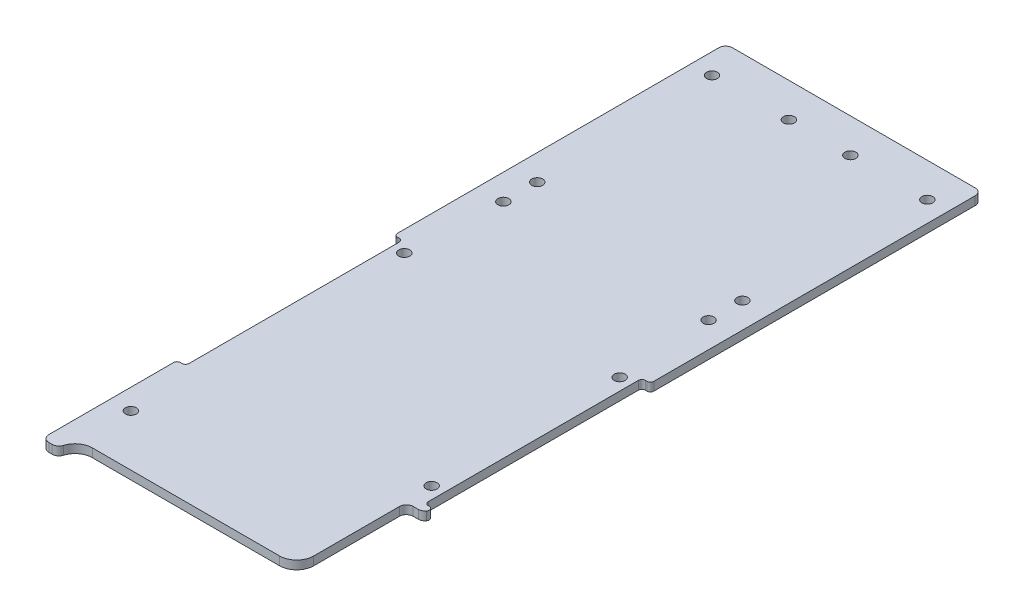
SolidWorks part; units mm, degrees
ref_plane "Front Plane" through (0, 0, 0) normal (0, 0, 1) x (1, 0, 0)
ref_plane "Top Plane" through (0, 0, 0) normal (0, 1, 0) x (1, 0, 0)
ref_plane "Right Plane" through (0, 0, 0) normal (1, 0, 0) x (0, 0, -1)
sketch "Sketch1" plane through (0, 0, 0) normal (0, 1, 0) x (1, 0, 0)
  line L0 (-39.9997, 0) -> (-39.9997, 114.3) construction
  line L1 (-47.625, 127) -> (47.625, 127)
  line L2 (-47.625, 127) -> (-47.625, -127)
  line L3 (-47.625, -127) -> (47.625, -127)
  line L4 (47.625, 127) -> (47.625, -127)
  line L5 (-47.625, 127) -> (47.625, -127) construction
  line L6 (-47.625, -127) -> (47.625, 127) construction
  line L7 (0, 0) -> (0, 127) construction
  line L8 (-39.9997, 0) -> (-39.9997, -101.6) construction
  line L9 (-39.9997, 0) -> (0, 0) construction
  line L10 (-41.275, -127) -> (-41.275, -120.65)
  line L11 (-41.275, -120.65) -> (41.275, -120.65)
  line L12 (41.275, -120.65) -> (41.275, -127)
  line L13 (-39.9997, 114.3) -> (-11.4247, 114.3) construction
  line L14 (39.9997, 114.3) -> (11.4247, 114.3) construction
  circle A0 centre (-39.9997, 114.3) radius 2.032
  circle A1 centre (-39.9997, 0) radius 2.032
  circle A2 centre (-39.9997, -101.6) radius 2.032
  circle A3 centre (39.9997, -101.6) radius 2.032
  circle A4 centre (39.9997, 0) radius 2.032
  circle A5 centre (39.9997, 114.3) radius 2.032
  circle A6 centre (-11.4247, 114.3) radius 2.032
  circle A7 centre (11.4247, 114.3) radius 2.032
  circle A8 centre (-39.9997, -69.85) radius 2.032
  circle A9 centre (39.9997, -69.85) radius 2.032
  point P0 (0, 0)
  dimension "D4" = 4.064
  dimension "D10" = 28.575
  dimension "D1" = 95.25
  dimension "D2" = 254
  dimension "D3" = 7.6253
  dimension "D5" = 12.7
  dimension "D6" = 25.4
  dimension "D7" = 6.35
  dimension "D8" = 6.35
  dimension "D9" = 6.35
  dimension "D11" = 69.85
extrude "Boss-Extrude1" add sketch "Sketch1" along normal blind 3.175 contours L4 L1 L2 L3 A4 A0 A1 A2 A3 A5 | A8 | A3 region at (0, 0, -2.6944) region at (39.9997, 0, 101.6) region at (-39.9997, 0, 69.85)
fillet "Fillet1" radius 2.54 4 edges at (-47.625, 1.5875, -127) (47.625, 1.5875, -127) (47.625, 1.5875, 127) (-47.625, 1.5875, 127)
fillet "Fillet2" radius 2.54 2 edges at (41.275, 1.5875, 127) (-41.275, 1.5875, 127)
fillet "Fillet3" radius 6.35 2 edges at (41.275, 1.5875, 120.65) (-41.275, 1.5875, 120.65)
sketch "Sketch2" plane through (0, 0, 0) normal (0, -1, 0) x (1, 0, 0)
  line L1 (43.815, 127) -> (45.085, 127) construction
  line L2 (40.6451, 123.5787) -> (40.6451, 79.8881)
  line L3 (40.6451, 79.8881) -> (47.625, 79.8881)
  line L11 (47.625, -124.46) -> (47.625, 124.46) construction
  line L12 (43.815, 127) -> (45.085, 127)
  line L13 (47.625, 79.8881) -> (47.625, 124.46)
  arc A0 (35.2956, 120.65) -> (41.3809, 125.1857) centre (35.2956, 127) ccw construction
  arc A1 (43.815, 127) -> (41.3809, 125.1857) centre (43.815, 124.46) ccw construction
  arc A2 (47.625, 124.46) -> (45.085, 127) centre (45.085, 124.46) ccw construction
  arc A3 (40.6451, 123.5787) -> (41.3809, 125.1857) centre (35.2956, 127) ccw
  arc A4 (43.815, 127) -> (41.3809, 125.1857) centre (43.815, 124.46) ccw
  arc A5 (47.625, 124.46) -> (45.085, 127) centre (45.085, 124.46) ccw
  dimension "D2" = 47.1119
  dimension "D1" = 6.9799
extrude "Cut-Extrude1" cut sketch "Sketch2" against normal through all
fillet "Fillet4" radius 6.35 1 edges at (40.6451, 1.5875, 123.5787)
fillet "Fillet5" radius 2.54 2 edges at (47.625, 1.5875, 79.8881) (40.6451, 1.5875, 79.8881)
sketch "Sketch3" plane through (0, 0, 0) normal (0, -1, 0) x (1, 0, 0)
  line L0 (-36.3032, -49.7791) -> (-39.91, -49.7791) construction
  line L1 (-40.418, -49.276) -> (-40.418, -45.7043) construction
  line L2 (-35.7952, -45.7043) -> (-35.7952, -49.276) construction
  line L3 (-39.91, -45.2013) -> (-36.3032, -45.2013) construction
  line L4 (-36.3032, -37.2027) -> (-39.91, -37.2027) construction
  line L5 (-35.7952, -33.1279) -> (-35.7952, -36.6996) construction
  line L6 (-40.418, -36.6996) -> (-40.418, -33.1279) construction
  line L7 (-39.91, -32.6249) -> (-36.3032, -32.6249) construction
  line L8 (36.29, -32.6249) -> (39.8968, -32.6249) construction
  line L9 (40.4048, -33.1279) -> (40.4048, -36.6996) construction
  line L10 (39.8968, -37.2027) -> (36.29, -37.2027) construction
  line L11 (35.782, -36.6996) -> (35.782, -33.1279) construction
  line L12 (36.29, -45.2013) -> (39.8968, -45.2013) construction
  line L13 (35.782, -49.276) -> (35.782, -45.7043) construction
  line L14 (40.4048, -45.7043) -> (40.4048, -49.276) construction
  line L15 (39.8968, -49.7791) -> (36.29, -49.7791) construction
  line L16 (-36.3032, -49.7791) -> (-39.91, -49.7791)
  line L17 (-40.418, -49.276) -> (-40.418, -45.7043)
  line L18 (-35.7952, -45.7043) -> (-35.7952, -49.276)
  line L19 (-39.91, -45.2013) -> (-36.3032, -45.2013)
  line L20 (-36.3032, -37.2027) -> (-39.91, -37.2027)
  line L21 (-35.7952, -33.1279) -> (-35.7952, -36.6996)
  line L22 (-40.418, -36.6996) -> (-40.418, -33.1279)
  line L23 (-39.91, -32.6249) -> (-36.3032, -32.6249)
  line L24 (36.29, -32.6249) -> (39.8968, -32.6249)
  line L25 (40.4048, -33.1279) -> (40.4048, -36.6996)
  line L26 (39.8968, -37.2027) -> (36.29, -37.2027)
  line L27 (35.782, -36.6996) -> (35.782, -33.1279)
  line L28 (36.29, -45.2013) -> (39.8968, -45.2013)
  line L29 (35.782, -49.276) -> (35.782, -45.7043)
  line L30 (40.4048, -45.7043) -> (40.4048, -49.276)
  line L31 (39.8968, -49.7791) -> (36.29, -49.7791)
  line L32 (-47.625, -25.836) -> (47.625, -25.836)
  line L33 (-47.625, -124.46) -> (-47.625, 124.46) construction
  line L34 (47.625, -124.46) -> (47.625, 77.3481) construction
  line L35 (0, -25.836) -> (0, -56.0686) construction
  line L1362 (-40.418, -34.9138) -> (-35.7952, -34.9138)
  line L1857 (-38.1066, -32.6249) -> (-38.1066, -37.2027)
  line L1858 (-38.1066, -45.2013) -> (-38.1066, -49.7791)
  line L1859 (-40.418, -47.4902) -> (-35.7952, -47.4902)
  circle A0 centre (-38.1066, -34.9138) radius 2.032
  circle A1 centre (-38.1066, -47.4902) radius 2.032
  circle A2 centre (38.1066, -47.4902) radius 2.032
  circle A3 centre (38.1066, -34.9138) radius 2.032
  ellipse E0 centre (-39.91, -45.7043) end of major axis (-39.402, -45.7043) minor radius 0.5031 (-39.91, -45.2013) -> (-40.418, -45.7043) ccw construction
  ellipse E1 centre (-39.91, -49.276) end of major axis (-39.402, -49.276) minor radius 0.5031 (-40.418, -49.276) -> (-39.91, -49.7791) ccw construction
  ellipse E6 centre (-36.3032, -49.276) end of major axis (-35.7952, -49.276) minor radius 0.5031 (-36.3032, -49.7791) -> (-35.7952, -49.276) ccw construction
  ellipse E7 centre (-36.3032, -45.7043) end of major axis (-35.7952, -45.7043) minor radius 0.5031 (-35.7952, -45.7043) -> (-36.3032, -45.2013) ccw construction
  ellipse E8 centre (-39.91, -36.6996) end of major axis (-39.402, -36.6996) minor radius 0.5031 (-40.418, -36.6996) -> (-39.91, -37.2027) ccw construction
  ellipse E9 centre (-36.3032, -36.6996) end of major axis (-35.7952, -36.6996) minor radius 0.5031 (-36.3032, -37.2027) -> (-35.7952, -36.6996) ccw construction
  ellipse E10 centre (-36.3032, -33.1279) end of major axis (-35.7952, -33.1279) minor radius 0.5031 (-35.7952, -33.1279) -> (-36.3032, -32.6249) ccw construction
  ellipse E11 centre (-39.91, -33.1279) end of major axis (-39.402, -33.1279) minor radius 0.5031 (-39.91, -32.6249) -> (-40.418, -33.1279) ccw construction
  ellipse E12 centre (39.8968, -33.1279) end of major axis (40.4048, -33.1279) minor radius 0.5031 (40.4048, -33.1279) -> (39.8968, -32.6249) ccw construction
  ellipse E13 centre (36.29, -33.1279) end of major axis (36.798, -33.1279) minor radius 0.5031 (36.29, -32.6249) -> (35.782, -33.1279) ccw construction
  ellipse E14 centre (39.8968, -36.6996) end of major axis (40.4048, -36.6996) minor radius 0.5031 (39.8968, -37.2027) -> (40.4048, -36.6996) ccw construction
  ellipse E15 centre (36.29, -36.6996) end of major axis (36.798, -36.6996) minor radius 0.5031 (35.782, -36.6996) -> (36.29, -37.2027) ccw construction
  ellipse E16 centre (36.29, -45.7043) end of major axis (36.798, -45.7043) minor radius 0.5031 (36.29, -45.2013) -> (35.782, -45.7043) ccw construction
  ellipse E17 centre (36.29, -49.276) end of major axis (36.798, -49.276) minor radius 0.5031 (35.782, -49.276) -> (36.29, -49.7791) ccw construction
  ellipse E18 centre (39.8968, -45.7043) end of major axis (40.4048, -45.7043) minor radius 0.5031 (40.4048, -45.7043) -> (39.8968, -45.2013) ccw construction
  ellipse E19 centre (39.8968, -49.276) end of major axis (40.4048, -49.276) minor radius 0.5031 (39.8968, -49.7791) -> (40.4048, -49.276) ccw construction
  ellipse E20 centre (-39.91, -45.7043) end of major axis (-39.402, -45.7043) minor radius 0.5031 (-39.91, -45.2013) -> (-40.418, -45.7043) ccw
  ellipse E21 centre (-39.91, -49.276) end of major axis (-39.402, -49.276) minor radius 0.5031 (-40.418, -49.276) -> (-39.91, -49.7791) ccw
  ellipse E22 centre (-36.3032, -49.276) end of major axis (-35.7952, -49.276) minor radius 0.5031 (-36.3032, -49.7791) -> (-35.7952, -49.276) ccw
  ellipse E23 centre (-36.3032, -45.7043) end of major axis (-35.7952, -45.7043) minor radius 0.5031 (-35.7952, -45.7043) -> (-36.3032, -45.2013) ccw
  ellipse E24 centre (-39.91, -36.6996) end of major axis (-39.402, -36.6996) minor radius 0.5031 (-40.418, -36.6996) -> (-39.91, -37.2027) ccw
  ellipse E25 centre (-36.3032, -36.6996) end of major axis (-35.7952, -36.6996) minor radius 0.5031 (-36.3032, -37.2027) -> (-35.7952, -36.6996) ccw
  ellipse E26 centre (-36.3032, -33.1279) end of major axis (-35.7952, -33.1279) minor radius 0.5031 (-35.7952, -33.1279) -> (-36.3032, -32.6249) ccw
  ellipse E27 centre (-39.91, -33.1279) end of major axis (-39.402, -33.1279) minor radius 0.5031 (-39.91, -32.6249) -> (-40.418, -33.1279) ccw
  ellipse E28 centre (39.8968, -33.1279) end of major axis (40.4048, -33.1279) minor radius 0.5031 (40.4048, -33.1279) -> (39.8968, -32.6249) ccw
  ellipse E29 centre (36.29, -33.1279) end of major axis (36.798, -33.1279) minor radius 0.5031 (36.29, -32.6249) -> (35.782, -33.1279) ccw
  ellipse E30 centre (39.8968, -36.6996) end of major axis (40.4048, -36.6996) minor radius 0.5031 (39.8968, -37.2027) -> (40.4048, -36.6996) ccw
  ellipse E31 centre (36.29, -36.6996) end of major axis (36.798, -36.6996) minor radius 0.5031 (35.782, -36.6996) -> (36.29, -37.2027) ccw
  ellipse E32 centre (36.29, -45.7043) end of major axis (36.798, -45.7043) minor radius 0.5031 (36.29, -45.2013) -> (35.782, -45.7043) ccw
  ellipse E33 centre (36.29, -49.276) end of major axis (36.798, -49.276) minor radius 0.5031 (35.782, -49.276) -> (36.29, -49.7791) ccw
  ellipse E34 centre (39.8968, -45.7043) end of major axis (40.4048, -45.7043) minor radius 0.5031 (40.4048, -45.7043) -> (39.8968, -45.2013) ccw
  ellipse E35 centre (39.8968, -49.276) end of major axis (40.4048, -49.276) minor radius 0.5031 (39.8968, -49.7791) -> (40.4048, -49.276) ccw
  dimension "D2" = 4.064
extrude "Cut-Extrude2" cut sketch "Sketch3" against normal through all contours A0 | A1 | A2 | A3
sketch "Sketch4" plane through (0, 3.175, 0) normal (0, 1, 0) x (1, 0, 0)
  line L11 (-47.625, 124.46) -> (-47.625, -124.46) construction
  line L12 (-47.625, -76.835) -> (-44.45, -76.835)
  line L13 (-47.625, -76.835) -> (-47.625, 3.81)
  line L15 (-47.625, 3.81) -> (-44.45, 3.81)
  line L16 (-44.45, -76.835) -> (-44.45, 3.81)
  line L17 (47.625, 124.46) -> (47.625, -77.3481) construction
  line L18 (47.625, -76.835) -> (44.45, -76.835)
  line L19 (47.625, -76.835) -> (47.625, 3.81)
  line L20 (47.625, 3.81) -> (44.45, 3.81)
  line L45 (44.45, -76.835) -> (44.45, 3.81)
  line L47 (43.1851, -79.8881) -> (45.085, -79.8881) construction
  dimension "D1" = 3.175
  dimension "D2" = 80.645
  dimension "D3" = 3.0531
extrude "Cut-Extrude3" cut sketch "Sketch4" against normal through all and the other way through all
fillet "Fillet6" radius 1.27 8 edges at (-44.45, 1.5875, -3.81) (-47.625, 1.5875, -3.81) (-47.625, 1.5875, 76.835) (-44.45, 1.5875, 76.835) (44.45, 1.5875, 76.835) (47.625, 1.5875, 76.835) (44.45, 1.5875, -3.81) (47.625, 1.5875, -3.81)
